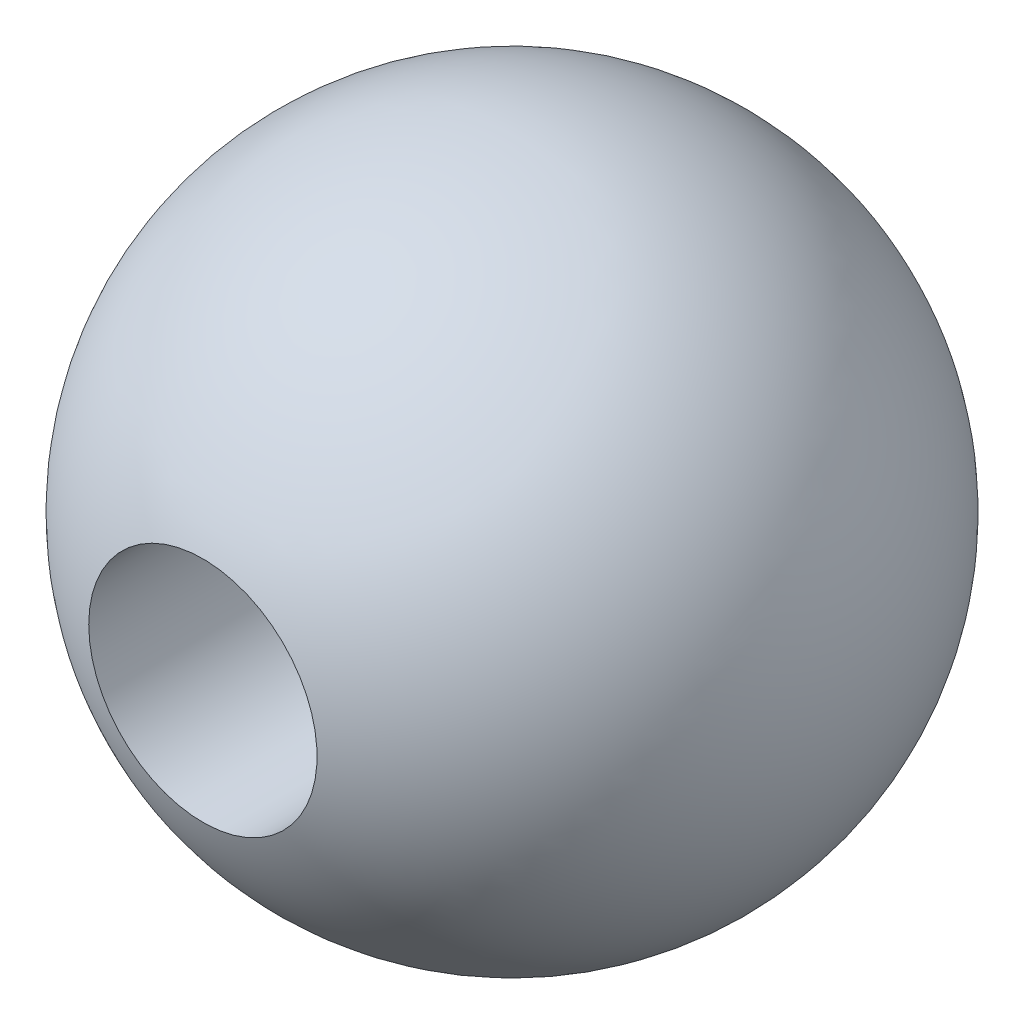
SolidWorks part; units mm, degrees
ref_plane "前视基准面" through (0, 0, 0) normal (0, 0, 1) x (1, 0, 0)
ref_plane "上视基准面" through (0, 0, 0) normal (0, 1, 0) x (1, 0, 0)
ref_plane "右视基准面" through (0, 0, 0) normal (1, 0, 0) x (0, 0, -1)
other "Configuration Table"
sketch "草图1" plane through (0, 0, 0) normal (0, 0, 1) x (1, 0, 0)
  line L1 (0, 2.165) -> (0, -2.165)
  arc A1 (0, 2.165) -> (0, -2.165) centre (0, 0) ccw
sketch "草图2" plane through (0, 0, 0) normal (0, 0, 1) x (1, 0, 0)
  circle A0 centre (0, 0) radius 0.75
revolve "旋转2" add sketch "草图1" angle 360 about L1
extrude "切除-拉伸2" cut sketch "草图2" against normal blind 5 and the other way blind 5
